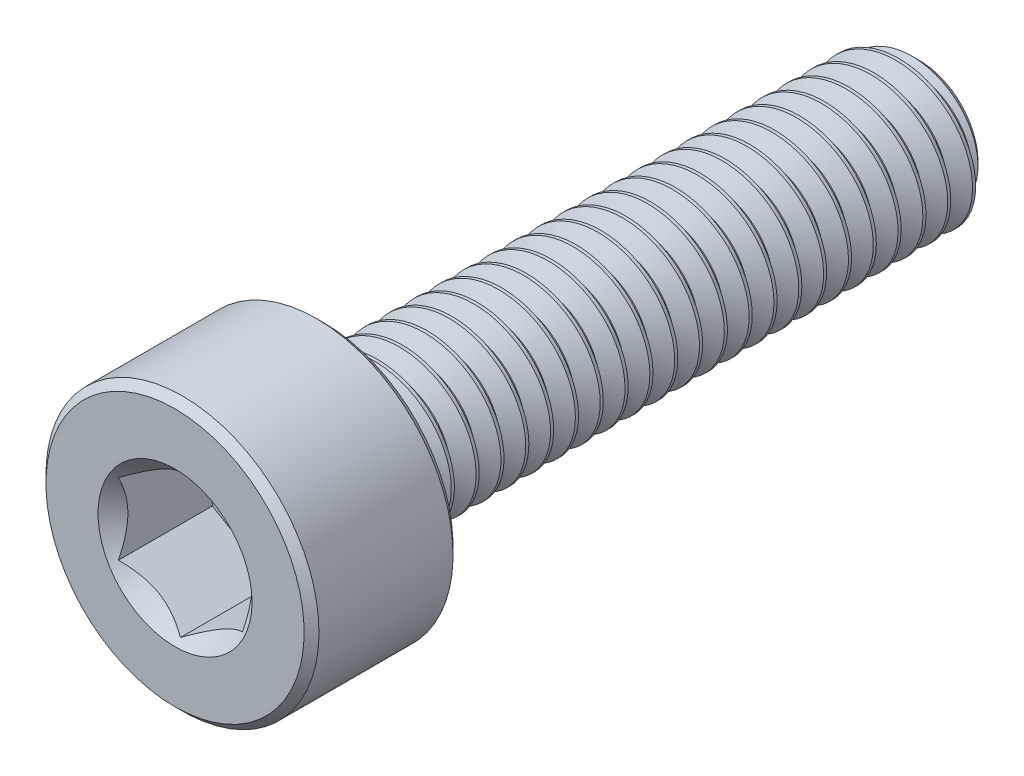
SolidWorks part; units mm, degrees
ref_plane "Front Plane" through (0, 0, 0) normal (0, 0, 1) x (1, 0, 0)
ref_plane "Top Plane" through (0, 0, 0) normal (0, 1, 0) x (1, 0, 0)
ref_plane "Right Plane" through (0, 0, 0) normal (1, 0, 0) x (0, 0, -1)
sketch "Sketch1" plane through (0, 0, 0) normal (1, 0, 0) x (0, 0, -1)
  line L0 (-7.5, 0) -> (7.5, 0) construction
  line L1 (7.5, 0) -> (7.5, 1.1752) construction
  line L2 (7.5, 1.1752) -> (7.1752, 1.5) construction
  line L3 (7.1752, 1.5) -> (7.125, 1.5) construction
  line L4 (7.125, 1.5) -> (-4.5, 1.5) construction
  line L5 (-4.5, 1.5) -> (-4.5, 2.75) construction
  line L6 (-4.5, 2.75) -> (-7.5, 2.75) construction
  line L7 (-7.5, 2.75) -> (-7.5, 0) construction
  line L8 (7.5, 1.1752) -> (7.5, 1.5) construction
  line L9 (7.4687, 1.5541) -> (7.7187, 1.1211) construction
  line L10 (7.7187, 1.1211) -> (7.9687, 1.5541) construction
  line L11 (7.9687, 1.5541) -> (7.4687, 1.5541) construction
  line L12 (7.7187, 1.5541) -> (7.7188, 1.5) construction
  line L13 (7.7187, 1.1211) -> (7.7187, 1.1752) construction
  line L14 (7.6875, 1.1752) -> (7.75, 1.1752) construction
  line L15 (7.5, 1.5) -> (7.9375, 1.5) construction
  line L16 (7.4844, 1.5271) -> (7.9531, 1.5271) construction
  line L17 (7.5, 0) -> (7.5, -1.5) construction
  line L18 (-4.65, 2.75) -> (-4.5, 2.6) construction
  line L19 (-7.35, 2.75) -> (-7.5, 2.6) construction
  line L20 (-4.5, 1.5) -> (-4.5, 0) construction
  line L21 (-4.5, 0.75) -> (-0.5, 0.75) construction
  line L22 (-0.5, 0.75) -> (3.5, 0.75) construction
  line L23 (3.5, 0.75) -> (7.5, 0.75) construction
  line L24 (-0.5, 0.75) -> (-0.5, 1.5) construction
  line L25 (-0.5, 1.5) -> (-0.5, 2.75) construction
  line L26 (3.5, 0.75) -> (3.5, 2.75) construction
  point P0 (-7.5, 1.25)
  point P3 (6.25, 1.5)
  point P4 (0, 0)
  point P18 (3.5, 1.5)
  point P22 (7.7187, 1.1752)
  point P24 (7.125, 1.5)
  point P25 (7.7188, 1.5)
  point P28 (7.7187, 1.5271)
  point P29 (6.25, -1.5)
  point P30 (-0.5, 1.5)
  point P31 (-6, 2.75)
  point P37 (-5.025, 2.75)
  point P38 (-7.275, 2.75)
  point P45 (-0.5, 0.75)
  point P46 (3.5, 0.75)
  dimension "D2" = 0.0625
  dimension "D7" = 0.15
  dimension "D8" = 0.15
  dimension "D9" = 0.15
  dimension "D10" = 0.075
  dimension "D11" = 0.375
  dimension "Drive Size" = 2.5
  dimension "Head Diameter" = 5.5
  dimension "Head Height" = 3
  dimension "Thread Pitch" = 0.5
  dimension "Thread Dia" = 3
  dimension "Length" = 12
  dimension "D12" = 0.375
  dimension "D4" = 1.25
  dimension "D3" = 45
sketch "Sketch2" plane through (0, 0, 0) normal (1, 0, 0) x (0, 0, -1)
  line L0 (-7.5, 0) -> (-7.5, 2.6)
  line L1 (-7.35, 2.75) -> (-4.65, 2.75)
  line L2 (-4.5, 2.6) -> (-4.5, 1.65)
  line L4 (7.1752, 1.5) -> (7.5, 1.1752)
  line L5 (7.5, 1.1752) -> (7.5, 0)
  line L6 (-4.5, 2.75) -> (-7.5, 2.75) construction
  line L7 (7.5, 0) -> (-7.5, 0)
  line L8 (-7.35, 2.75) -> (-7.5, 2.6) construction
  line L10 (-7.35, 2.75) -> (-7.5, 2.6)
  line L14 (-4.65, 2.75) -> (-4.5, 2.6) construction
  line L16 (-4.65, 2.75) -> (-4.5, 2.6)
  line L17 (-4.5, 1.5) -> (-4.5, 2.75) construction
  line L19 (-4.35, 1.5) -> (7.1752, 1.5)
  line L20 (7.125, 1.5) -> (-4.5, 1.5) construction
  arc A1 (-4.5, 1.65) -> (-4.35, 1.5) centre (-4.35, 1.65) ccw
  dimension "D3" = 0.15
revolve "Revolve1" add sketch "Sketch2" angle 360 about L7
sketch "Sketch3" plane through (0, 0, 7.5) normal (0, 0, 1) x (1, 0, 0)
  line L1 (1.25, -0.7217) -> (1.25, 0.7217)
  line L2 (1.25, 0.7217) -> (0, 1.4434)
  line L3 (0, 1.4434) -> (-1.25, 0.7217)
  line L4 (-1.25, 0.7217) -> (-1.25, -0.7217)
  line L5 (-1.25, -0.7217) -> (0, -1.4434)
  line L6 (0, -1.4434) -> (1.25, -0.7217)
  circle A0 centre (0, 0) radius 1.25 construction
  circle A1 centre (0, 0) radius 2.75 construction
  circle A2 centre (0, 0) radius 2.75 construction
  circle A3 centre (0, 0) radius 1.4434 construction
  point P13 (0, 0)
  dimension "D1" = 2.8868
extrude "Cut-Extrude1" cut sketch "Sketch3" against normal offset from surface (2 mm away) 1 up to face at (0, 2.6, 4.5)
sketch "Sketch4" plane through (0, 0, 7.5) normal (0, 0, 1) x (1, 0, 0)
  circle A0 centre (0, 0) radius 1.5516
  dimension "D1" = 3.1033
extrude "Cut-Extrude2" cut sketch "Sketch4" against normal up to vertex (1.5 mm away) draft 45 up to point (0, 2.75, 6)
sketch "Sketch11" plane through (0, 0, 0) normal (1, 0, 0) x (0, 0, -1)
  line L0 (-7.5, 0) -> (7.5, 0) construction
  line L1 (-7.5, 0) -> (7.5, 0) construction
  line L2 (-2.25, 0) -> (-2.25, 1.5) construction
  line L3 (7.125, 1.5) -> (-4.5, 1.5) construction
  line L4 (5.25, 0) -> (5.25, 1.5) construction
  line L6 (7.5, 1.1752) -> (7.5, 1.5) construction
  point P2 (-2.25, 0)
  point P3 (5.25, 0)
  dimension "D1" = 2.25
  dimension "D2" = 2.25
sketch "Sketch6" plane through (0, 0, -7.5) normal (0, 0, -1) x (-1, 0, 0)
  circle A0 centre (0, 0) radius 1.5
curve "Helix/Spiral1" pitch 0.5 height 12.5 radius 1.5 centre (0, 0, -7.5) axis (0, 0, 1) start towards (0, 1, 0)
sketch "Sketch10" plane through (0, 0, 0) normal (1, 0, 0) x (0, 0, -1)
  line L0 (-4.35, -2.75) -> (-4.35, 2.75)
  line L5 (-7.5, 0) -> (7.5, 0) construction
  line L6 (-4.35, 1.5) -> (-4.35, -1.5) construction
  point P3 (-4.35, 0)
split "Split1" trim tools "Sketch10" bodies to split 106 resulting bodies 114 115
sketch "Sketch7" plane through (0, 0, 0) normal (1, 0, 0) x (0, 0, -1)
  line L0 (7.4844, 1.5271) -> (7.9531, 1.5271)
  line L1 (7.9531, 1.5271) -> (7.75, 1.1752)
  line L2 (7.75, 1.1752) -> (7.6875, 1.1752)
  line L3 (7.6875, 1.1752) -> (7.4844, 1.5271)
sweep "Cut-Sweep1" cut profiles "Sketch7" path "Helix/Spiral1" align with end faces yes
sketch "Sketch8" plane through (0, 0, 0) normal (1, 0, 0) x (0, 0, -1)
  line L0 (-4.5, 0) -> (-4.5, 1.5)
  line L1 (-4.35, -1.5) -> (-4.35, 1.5) construction
  line L2 (-4.5, 1.5) -> (-4.35, 1.5)
  line L4 (-4.35, 1.5) -> (-3.484, 0)
  line L5 (-3.484, 0) -> (-4.5, 0)
  line L6 (7.125, 1.5) -> (-4.5, 1.5) construction
  line L7 (-7.5, 0) -> (7.5, 0) construction
  dimension "D1" = 60
revolve "Revolve2" add sketch "Sketch8" angle 360 about L5
equation "\"D2@Sketch1\" = \"Thread Pitch@Sketch1\" / 8"
equation "\"D4@Helix/Spiral1\" = \"Thread Pitch@Sketch1\""
equation "\"D7@Sketch1\" = \"Head Height@Sketch1\" * .05"
equation "\"D8@Sketch1\"=\"D7@Sketch1\""
equation "\"D9@Sketch1\"=\"D7@Sketch1\""
equation "\"D10@Sketch1\"=\"D7@Sketch1\"/2"
equation "\"D11@Sketch1\"=\"D10@Sketch1\"*5"
equation "\"D4@Sketch1\"=\"Thread Pitch@Sketch1\"*2.5"
equation "\"D12@Sketch1\"=\"Thread Pitch@Sketch1\"*.75"
equation "\"D3@Helix/Spiral1\"=\"Length@Sketch1\"+\"Thread Pitch@Sketch1\""
equation "\"D3@Sketch2\"=\"Thread Dia@Sketch1\"*0.05"
equation "\"D1@Sketch11\"=\"Length@Sketch1\"*0.1875"
equation "\"D2@Sketch11\"=\"D1@Sketch11\""
equation "\"D1@Sketch4\"=\"D1@Sketch3\"*1.075"
